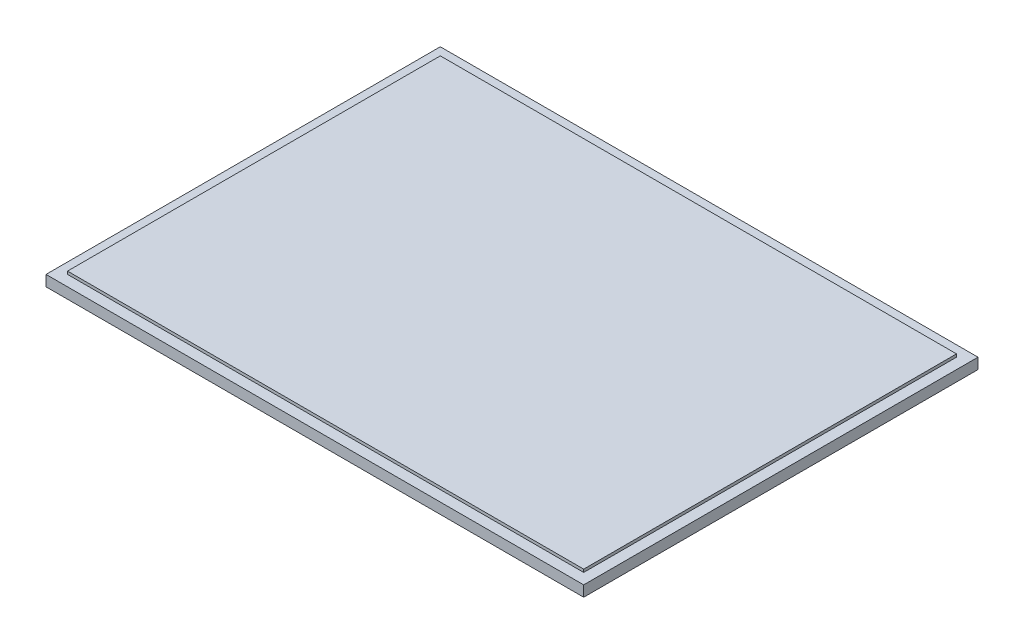
SolidWorks part; units mm, degrees
ref_plane "Front Plane" through (0, 0, 0) normal (0, 0, 1) x (1, 0, 0)
ref_plane "Top Plane" through (0, 0, 0) normal (0, 1, 0) x (1, 0, 0)
ref_plane "Right Plane" through (0, 0, 0) normal (1, 0, 0) x (0, 0, -1)
sketch "Sketch1" plane through (0, 0, 0) normal (0, 1, 0) x (1, 0, 0)
  line L0 (-375, 275) -> (375, 275)
  line L1 (-380, -280) -> (380, -280) construction
  line L2 (-380, -280) -> (-380, 280) construction
  line L3 (-380, 280) -> (380, 280) construction
  line L4 (380, -280) -> (380, 280) construction
  line L5 (-380, -280) -> (380, 280) construction
  line L6 (-380, 280) -> (380, -280) construction
  line L7 (375, -275) -> (375, 275)
  line L8 (-375, -275) -> (375, -275)
  line L9 (-375, -275) -> (-375, 275)
  point P0 (0, 0)
  dimension "D1" = 760
  dimension "D2" = 560
  dimension "D3" = 5
extrude "Boss-Extrude1" add sketch "Sketch1" along normal blind 19
sketch "Sketch2" plane through (0, 19, 0) normal (0, 1, 0) x (1, 0, 0)
  line L0 (375, 275) -> (-375, 275) construction
  line L5 (-370, 0) -> (370, 0) construction
  line L7 (-370, -270) -> (370, -270) construction
  line L8 (-370, -270) -> (-370, 270) construction
  line L9 (-370, 270) -> (370, 270) construction
  line L10 (370, -270) -> (370, 270) construction
  line L11 (-370, -270) -> (370, 270) construction
  line L12 (-370, 270) -> (370, -270) construction
  line L13 (375, -275) -> (375, 275) construction
  line L14 (0, 270) -> (0, -270) construction
  circle A1 centre (-370, 270) radius 1.5
  circle A2 centre (-185, 270) radius 1.5
  circle A3 centre (0, 270) radius 1.5
  circle A4 centre (185, 270) radius 1.5
  circle A5 centre (370, 270) radius 1.5
  circle A6 centre (-370, 90) radius 1.5
  circle A7 centre (-370, -90) radius 1.5
  circle A8 centre (-370, -270) radius 1.5
  circle A9 centre (370, -270) radius 1.5
  circle A10 centre (185, -270) radius 1.5
  circle A11 centre (0, -270) radius 1.5
  circle A12 centre (-185, -270) radius 1.5
  circle A13 centre (-370, -270) radius 1.5
  circle A14 centre (370, -90) radius 1.5
  circle A15 centre (370, 90) radius 1.5
  point P0 (0, 0)
  point P6 (0, 0)
  dimension "D1" = 3
  dimension "D2" = 5
  dimension "D3" = 5
  dimension "D4" = 5
  dimension "D5" = 4
extrude "Cut-Extrude1" [suppressed] cut sketch "Sketch2" against normal through all contours A1 | A2 | A3 | A4 | A5 | A15 | A14 | A9 | A10 | A11 | A12 | A8 | A7 | A6
sketch "Sketch3" plane through (0, 19, 0) normal (0, 1, 0) x (1, 0, 0)
  line L8 (-360, 260) -> (-360, -260)
  line L9 (-360, -260) -> (360, -260)
  line L10 (360, -260) -> (360, 260)
  line L11 (360, 260) -> (-360, 260)
  line L12 (-360, 260) -> (-360, -260)
  line L13 (-360, -260) -> (360, -260)
  line L14 (360, -260) -> (360, 260)
  line L15 (360, 260) -> (-360, 260)
  line L16 (-375, 275) -> (-375, -275)
  line L17 (-375, -275) -> (375, -275)
  line L18 (375, -275) -> (375, 275)
  line L19 (375, 275) -> (-375, 275)
  line L20 (-375, 275) -> (-375, -275)
  line L21 (-375, -275) -> (375, -275)
  line L22 (375, -275) -> (375, 275)
  line L23 (375, 275) -> (-375, 275)
  dimension "D1" = 15
  dimension "D2" = 0
extrude "Cut-Extrude2" cut sketch "Sketch3" against normal blind 4
equation "\"Crossbar_Width\"= 80mm"
equation "\"Vertical_Offset\"= \"Crossbar_Width\" / 2"
equation "\"Toolhead_Width\"= 100mm"
equation "\"Mechanical_Buffer\"= 30mm"
equation "\"Z_Interstitial\"= 100mm"
equation "\"Z_Interstitial_Sketch\"= \"Z_Interstitial\" + 1in"
